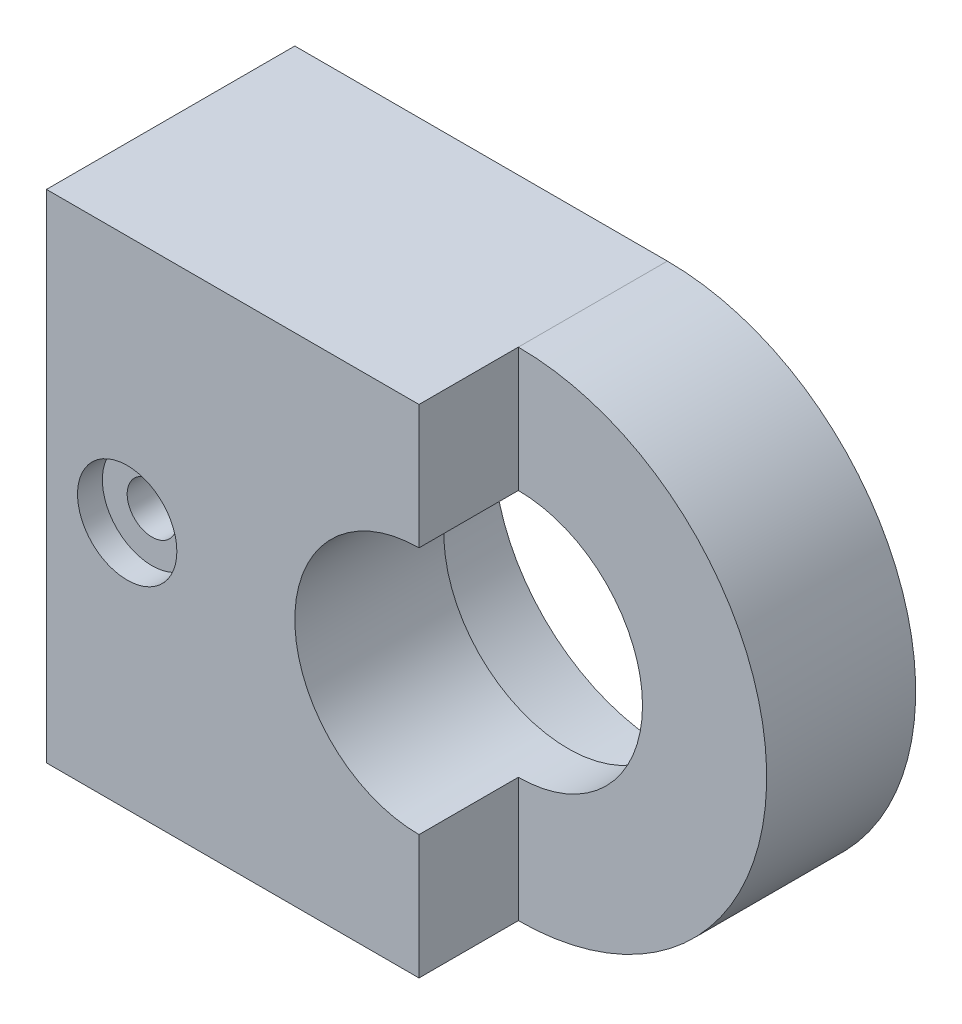
SolidWorks part; units mm, degrees
ref_plane "Plan de face" through (0, 0, 0) normal (0, 0, 1) x (1, 0, 0)
ref_plane "Plan de dessus" through (0, 0, 0) normal (0, 1, 0) x (1, 0, 0)
ref_plane "Plan de droite" through (0, 0, 0) normal (1, 0, 0) x (0, 0, -1)
sketch "Esquisse1" plane through (0, 0, 0) normal (0, 0, 1) x (1, 0, 0)
  line L0 (0, 20) -> (-30, 20)
  line L1 (-30, 20) -> (-30, -20)
  line L2 (-30, -20) -> (0, -20)
  line L3 (20, 0) -> (-30, 0) construction
  arc A0 (0, -20) -> (0, 20) centre (0, 0) ccw
  circle A1 centre (0, 0) radius 14
  circle A2 centre (-23.5, 0) radius 2
  circle A3 centre (-23.5, 0) radius 4
  dimension "D1" = 40
  dimension "D3" = 28
  dimension "D4" = 4
  dimension "D6" = 8
  dimension "D2" = 30
  dimension "D5" = 6.5
extrude "Boss.-Extru.1" add sketch "Esquisse1" along normal blind 20 contours L0 L1 L2 A0
extrude "Enlèv. mat.-Extru.1" cut sketch "Esquisse1<4>" along normal blind 8 contours A1
sketch "Esquisse1<4>" plane through (0, 0, 0) normal (0, 0, 1) x (1, 0, 0) same geometry as "Esquisse1"
sketch "Esquisse3" plane through (-30, 0, 0) normal (-1, 0, 0) x (0, 0, 1)
  line L0 (0, 0) -> (20, 0) construction
  line L1 (20, 20) -> (20, -20) construction
  circle A0 centre (10, 0) radius 5
  dimension "D1" = 10
extrude "Enlèv. mat.-Extru.2" cut sketch "Esquisse3" against normal blind 14
extrude "Enlèv. mat.-Extru.3" cut sketch "Esquisse1<5>" against normal through all and the other way through all contours A2
sketch "Esquisse1<5>" plane through (0, 0, 0) normal (0, 0, 1) x (1, 0, 0) same geometry as "Esquisse1"
extrude "Enlèv. mat.-Extru.4" cut sketch "Esquisse1<6>" along normal blind 2 contours A3
sketch "Esquisse1<6>" plane through (0, 0, 0) normal (0, 0, 1) x (1, 0, 0) same geometry as "Esquisse1"
extrude "Enlèv. mat.-Extru.5" cut sketch "Esquisse1<7>" against normal blind 2 from surface contours A3 starting at face at (-21.5, 0, 20)
sketch "Esquisse1<7>" plane through (0, 0, 0) normal (0, 0, 1) x (1, 0, 0) same geometry as "Esquisse1"
sketch "Esquisse4" plane through (0, 0, 20) normal (0, 0, 1) x (1, 0, 0)
  circle A0 centre (0, 0) radius 10
  dimension "D1" = 20
extrude "Enlèv. mat.-Extru.6" cut sketch "Esquisse4" against normal up to next
sketch "Esquisse5" plane through (0, 0, 20) normal (0, 0, 1) x (1, 0, 0)
  line L0 (0, 10) -> (0, 20)
  line L1 (0, -20) -> (0, -10)
  arc A1 (0, 10) -> (0, -10) centre (0, 0) ccw
  circle A3 centre (0, 0) radius 10 construction
  arc A4 (0, 20) -> (0, -20) centre (0, 0) cw
  arc A5 (0, -20) -> (0, 20) centre (0, 0) ccw construction
extrude "Enlèv. mat.-Extru.7" cut sketch "Esquisse5" against normal blind 8
